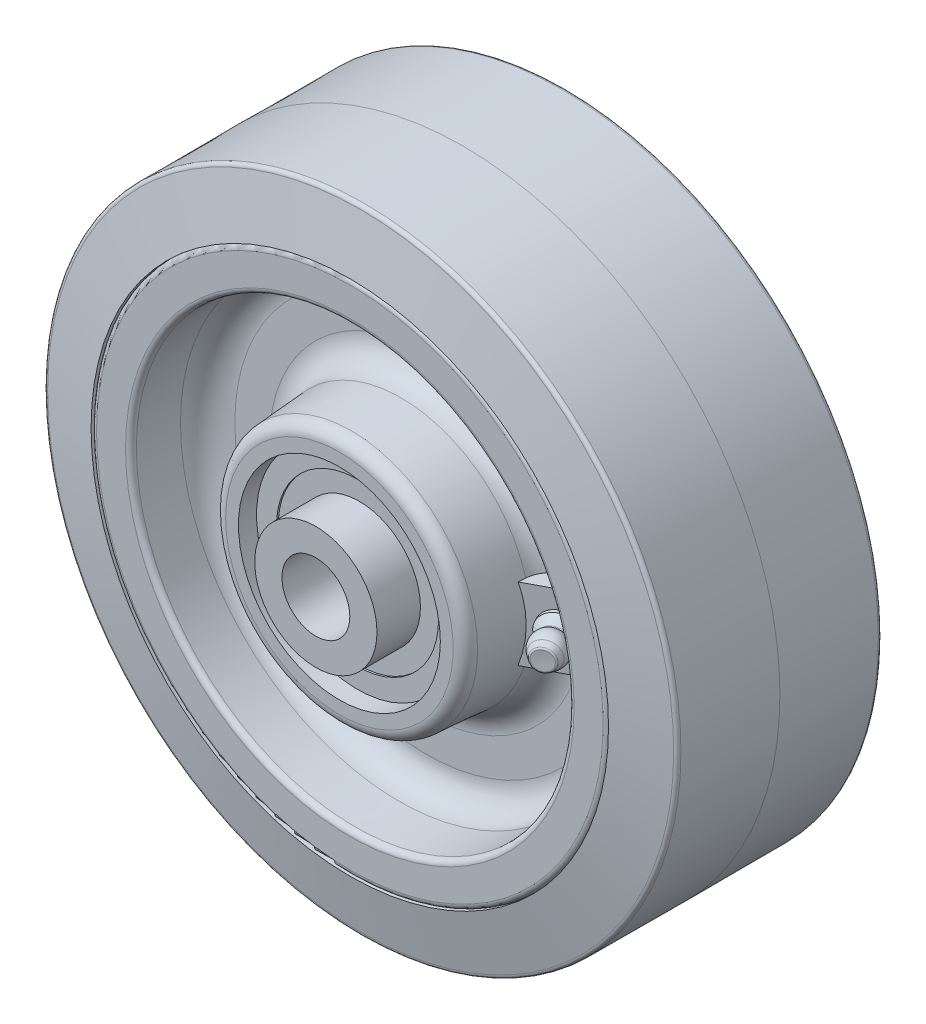
SolidWorks part; units mm, degrees
ref_plane "Front Plane" through (0, 0, 0) normal (0, 0, 1) x (1, 0, 0)
ref_plane "Top Plane" through (0, 0, 0) normal (0, 1, 0) x (1, 0, 0)
ref_plane "Right Plane" through (0, 0, 0) normal (1, 0, 0) x (0, 0, -1)
sketch "Sketch1" plane through (0, 0, 0) normal (1, 0, 0) x (0, 0, -1)
  line L0 (-20.6375, 0) -> (20.6375, 0) construction
  line L1 (0, -44.45) -> (0, 44.45) construction
  line L2 (20.6375, -4.7625) -> (20.6375, 4.7625) construction
  line L3 (-20.6375, -4.7625) -> (-20.6375, 4.7625) construction
  line L4 (-15.875, 0) -> (15.875, 0) construction
  line L5 (-20.6375, 4.7625) -> (-20.6375, 8.5725) construction
  line L6 (20.6375, 4.7625) -> (20.6375, 8.5725) construction
  line L7 (20.6375, -4.7625) -> (20.6375, -8.5725) construction
  line L8 (-20.6375, -4.7625) -> (-20.6375, -8.5725) construction
  point P4 (0, 0)
  point P8 (0, 0)
  point P11 (20.6375, 0)
  point P14 (-20.6375, 0)
  point P17 (0, 0)
  point P19 (-20.6375, 8.5725)
  point P20 (20.6375, 8.5725)
  point P22 (20.6375, -8.5725)
  point P23 (-20.6375, -8.5725)
  point P25 (20.6375, -4.7625)
  point P26 (20.6375, 4.7625)
  dimension "Axle Diameter" = 9.525
  dimension "Wheel Diameter" = 88.9
  dimension "Hub Length" = 41.275
  dimension "Wheel Width" = 31.75
  dimension "D1" = 3.81
sketch "Sketch7" plane through (0, 0, 0) normal (0, 0, 1) x (1, 0, 0)
  line L0 (-44.45, 0) -> (44.45, 0) construction
  line L1 (-4.7625, 0) -> (4.7625, 0) construction
  point P3 (-44.45, 0)
  point P4 (0, 0)
  point P5 (44.45, 0)
  point P9 (0, 0)
  point P10 (4.7625, 0)
  point P12 (-4.7625, 0)
  dimension "D1" = 88.9
  dimension "D2" = 9.525
sketch "Sketch2" plane through (0, 0, 0) normal (1, 0, 0) x (0, 0, -1)
  line L2 (20.6375, 4.7625) -> (-20.6375, 4.7625)
  line L3 (20.6375, 4.7625) -> (20.6375, 8.5725)
  line L4 (20.6375, 8.5725) -> (-20.6375, 8.5725)
  line L5 (-20.6375, 4.7625) -> (-20.6375, 8.5725)
  dimension "D1" = 3.81
revolve "Revolve1" add sketch "Sketch2" angle 360 about L0
sketch "Sketch3" plane through (0, 0, 0) normal (1, 0, 0) x (0, 0, -1)
  line L0 (20.6375, 8.5725) -> (-20.6375, 8.5725) construction
  line L1 (-14.5415, 8.5725) -> (14.5415, 8.5725)
  line L2 (-14.5415, 8.5725) -> (-14.5415, 11.3665)
  line L3 (-14.5415, 11.3665) -> (14.5415, 11.3665)
  line L4 (14.5415, 8.5725) -> (14.5415, 11.3665)
  line L5 (20.6375, -8.5725) -> (20.6375, 8.5725) construction
  line L6 (-20.6375, 8.5725) -> (-20.6375, -8.5725) construction
  dimension "D1" = 6.096
  dimension "D2" = 6.096
  dimension "D3" = 2.794
revolve "Revolve2" add sketch "Sketch3" angle 360 about L0
sketch "Sketch4" plane through (0, 0, 0) normal (1, 0, 0) x (0, 0, -1)
  line L0 (14.5415, 11.3665) -> (-14.5415, 11.3665) construction
  line L1 (14.7955, 11.3665) -> (-14.7955, 11.3665)
  line L2 (14.7955, 11.3665) -> (14.7955, 14.1605)
  line L3 (14.7955, 14.1605) -> (-14.7955, 14.1605)
  line L4 (-14.7955, 11.3665) -> (-14.7955, 14.1605)
  line L5 (14.5415, -11.3665) -> (14.5415, 11.3665) construction
  line L6 (-14.5415, 11.3665) -> (-14.5415, -11.3665) construction
  dimension "D1" = 0.254
  dimension "D2" = 0.254
  dimension "D3" = 2.794
revolve "Revolve3" add sketch "Sketch4" angle 360 about L0
sketch "Sketch5" plane through (0, 0, 0) normal (1, 0, 0) x (0, 0, -1)
  line L2 (17.3355, 14.1605) -> (17.3355, 15.9385)
  line L5 (14.7955, -14.1605) -> (14.7955, 14.1605) construction
  line L6 (-17.3355, 14.1605) -> (17.3355, 14.1605)
  line L7 (17.3355, 15.9385) -> (17.3355, 17.7165)
  line L8 (17.3355, 17.7165) -> (15.8115, 17.7165)
  line L9 (15.8115, 17.7165) -> (8.6995, 18.2245)
  line L10 (8.6995, 18.2245) -> (5.1435, 18.2245)
  line L11 (5.1435, 18.2245) -> (5.1435, 22.0345)
  line L12 (5.1435, 22.0345) -> (5.1435, 26.8605)
  line L13 (5.1435, 26.8605) -> (5.1435, 30.6705)
  line L14 (5.1435, 30.6705) -> (8.9535, 30.6705)
  line L15 (8.9535, 30.6705) -> (15.113, 30.6959)
  line L16 (15.113, 30.6959) -> (15.875, 30.6959)
  line L17 (15.875, 30.6959) -> (15.875, 31.4579)
  line L18 (15.875, 31.4579) -> (15.875, 35.5219)
  line L19 (15.875, 35.5219) -> (15.875, 36.2839)
  line L20 (15.875, 36.2839) -> (15.113, 36.2839)
  line L23 (0, -44.45) -> (0, 44.45) construction
  line L24 (14.7955, 14.1605) -> (-14.7955, 14.1605) construction
  line L40 (15.113, 36.2839) -> (-15.113, 36.2839)
  line L41 (-15.875, 36.2839) -> (-15.113, 36.2839)
  line L42 (-15.875, 35.5219) -> (-15.875, 36.2839)
  line L43 (-15.875, 31.4579) -> (-15.875, 35.5219)
  line L44 (-15.875, 30.6959) -> (-15.875, 31.4579)
  line L45 (-15.113, 30.6959) -> (-15.875, 30.6959)
  line L46 (-8.9535, 30.6705) -> (-15.113, 30.6959)
  line L47 (-5.1435, 30.6705) -> (-8.9535, 30.6705)
  line L48 (-5.1435, 26.8605) -> (-5.1435, 30.6705)
  line L49 (-5.1435, 22.0345) -> (-5.1435, 26.8605)
  line L50 (-5.1435, 18.2245) -> (-5.1435, 22.0345)
  line L51 (-8.6995, 18.2245) -> (-5.1435, 18.2245)
  line L52 (-15.8115, 17.7165) -> (-8.6995, 18.2245)
  line L53 (-17.3355, 17.7165) -> (-15.8115, 17.7165)
  line L54 (-17.3355, 15.9385) -> (-17.3355, 17.7165)
  line L55 (-17.3355, 14.1605) -> (-17.3355, 15.9385)
  point P8 (0, 36.2839)
  point P31 (0, 0)
  point P43 (-15.875, 36.2839)
  point P44 (15.875, 36.2839)
  dimension "D1" = 2.54
  dimension "D3" = 1.778
  dimension "D4" = 1.778
  dimension "D5" = 1.524
  dimension "D6" = 0.508
  dimension "D7" = 7.112
  dimension "D8" = 3.556
  dimension "D9" = 3.81
  dimension "Thickness IW" = 4.826
  dimension "D11" = 3.81
  dimension "D12" = 3.81
  dimension "D14" = 0.0254
  dimension "D15" = 0.762
  dimension "D16" = 0.762
  dimension "Thickness MW" = 4.064
  dimension "D18" = 0.762
  dimension "D19" = 0.762
revolve "Revolve4" add sketch "Sketch5" angle 360 about L0
sketch "Sketch6" plane through (0, 0, 0) normal (1, 0, 0) x (0, 0, -1)
  line L0 (-15.875, 36.2839) -> (15.875, 36.2839)
  line L2 (0, -44.45) -> (0, 44.45) construction
  line L4 (15.113, 36.2839) -> (-15.113, 36.2839) construction
  line L5 (15.875, 36.2839) -> (14.351, 43.9039)
  line L6 (14.351, 43.9039) -> (14.351, 44.4119)
  line L7 (14.351, 44.4119) -> (13.843, 44.4119)
  line L8 (13.843, 44.4119) -> (0, 44.45)
  line L9 (0, -44.45) -> (0, 44.45) construction
  line L11 (-13.843, 44.4119) -> (0, 44.45)
  line L12 (-14.351, 44.4119) -> (-13.843, 44.4119)
  line L13 (-14.351, 43.9039) -> (-14.351, 44.4119)
  line L14 (-15.875, 36.2839) -> (-14.351, 43.9039)
  point P3 (0, 36.2839)
  point P15 (0, 0)
  dimension "D1" = 31.75
  dimension "Thickness OW" = 7.62
  dimension "D3" = 1.524
  dimension "D4" = 0.508
  dimension "D5" = 0.508
revolve "Revolve6" add sketch "Sketch6" angle 360 about L0
fillet "Fillet1" radius 0.762 2 edges at (36.2839, 0, 15.875) (36.2839, 0, -15.875)
fillet "Fillet2" radius 0.508 2 edges at (44.4119, 0, 14.351) (44.4119, 0, -14.351)
fillet "Fillet3" radius 3.81 4 edges at (18.2245, 0, -5.1435) (30.6705, 0, -5.1435) (18.2245, 0, 5.1435) (30.6705, 0, 5.1435)
fillet "Fillet4" radius 0.762 2 edges at (30.6959, 0, 15.875) (30.6959, 0, -15.875)
fillet "Fillet5" radius 1.778 2 edges at (17.7165, 0, 17.3355) (17.7165, 0, -17.3355)
sketch "Sketch8" plane through (0, 0, 5.1435) normal (0, 0, 1) x (1, 0, 0)
  line L0 (16.9821, -5.08) -> (16.9821, 5.08)
  line L4 (-44.45, 0) -> (44.45, 0) construction
  line L5 (16.9821, 5.08) -> (25.1101, 5.08)
  line L6 (16.9821, -5.08) -> (25.1101, -5.08)
  line L7 (25.1101, 5.08) -> (25.1101, -5.08)
  circle A2 centre (0, 0) radius 17.7256 construction
  point P3 (16.9821, 0)
  dimension "D1" = 10.16
  dimension "D2" = 8.128
extrude "Boss-Extrude1" add sketch "Sketch8" along normal blind 4.572
chamfer "Chamfer1" distance 7.6835 angle 28 1 edges at (25.1101, 0, 9.7155) first distance on face at (21.4497, 0, 9.7155)
fillet "Fillet6" radius 2.54 1 edges at (25.1101, 0, 5.6301)
sketch "Sketch10" plane through (7.8681, 16.6307, 14.7978) normal (0.4695, 0, 0.8829) x (0.7785, -0.4718, -0.4139)
  line L0 (23.3472, -6.3694) -> (24.0191, -6.0099) construction
  line L3 (26.4157, -10.489) -> (21.6224, -1.5308) construction
  line L4 (26.4157, -10.489) -> (19.7878, -14.0354) construction
  line L5 (23.3472, -6.3694) -> (18.8681, -8.766) construction
  point P7 (24.0191, -6.0099)
  dimension "D1" = 0.762
  dimension "D2" = 5.08
sketch "Sketch11" plane through (0, 0, 0) normal (0, 1, 0) x (1, 0, 0)
  line L0 (23.3909, -6.5442) -> (21.1482, -7.7367)
  line L1 (23.3909, -6.5442) -> (18.9055, -8.9291) construction
  line L2 (21.1482, -7.7367) -> (23.6524, -12.4463)
  line L3 (23.3909, -6.5442) -> (23.6294, -6.9927)
  line L4 (23.6294, -6.9927) -> (23.6294, -8.2627)
  line L5 (23.6294, -8.2627) -> (23.6294, -8.7707)
  line L6 (23.6294, -8.7707) -> (23.8834, -8.7707)
  line L7 (23.8834, -8.7707) -> (25.8377, -12.4463) construction
  line L8 (24.9566, -10.7892) -> (24.982, -11.8052)
  line L9 (24.982, -11.8052) -> (23.6524, -12.4463)
  arc A0 (23.8834, -8.7707) -> (24.9566, -10.7892) centre (22.9366, -10.5687) cw
  dimension "D9" = 2.032
  dimension "D1" = 2.54
  dimension "D2" = 5.334
  dimension "D3" = 0.508
  dimension "D4" = 1.27
  dimension "D6" = 0.508
  dimension "D7" = 0.254
  dimension "D8" = 2.286
  dimension "D10" = 1.016
  dimension "D11" = 0.0254
revolve "Revolve7" add sketch "Sketch11" angle 360 about L2
fillet "Fillet7" radius 0.254 1 edges at (20.618, 0, 10.3719)
fillet "Fillet8" radius 0.254 1 edges at (22.3773, 0, 13.1901)
equation "\"D1@Sketch7\"=\"Wheel Diameter@Sketch1\""
equation "\"D2@Sketch7\"=\"Axle Diameter@Sketch1\""
